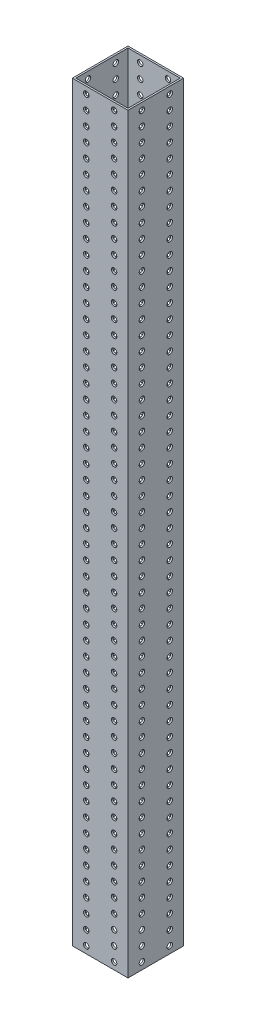
SolidWorks part; units mm, degrees
ref_plane "Front Plane" through (0, 0, 0) normal (0, 0, 1) x (1, 0, 0)
ref_plane "Top Plane" through (0, 0, 0) normal (0, 1, 0) x (1, 0, 0)
ref_plane "Right Plane" through (0, 0, 0) normal (1, 0, 0) x (0, 0, -1)
sketch "Sketch1" plane through (0, 0, 0) normal (0, 1, 0) x (1, 0, 0)
  line L1 (-25.4, 25.4) -> (25.4, 25.4)
  line L2 (-25.4, 25.4) -> (-25.4, -25.4)
  line L3 (-25.4, -25.4) -> (25.4, -25.4)
  line L4 (25.4, 25.4) -> (25.4, -25.4)
  line L5 (-25.4, 25.4) -> (25.4, -25.4) construction
  line L6 (-25.4, -25.4) -> (25.4, 25.4) construction
  line L7 (23.8125, 23.8125) -> (-23.8125, 23.8125)
  line L8 (23.8125, 23.8125) -> (23.8125, -23.8125)
  line L9 (23.8125, -23.8125) -> (-23.8125, -23.8125)
  line L10 (-23.8125, 23.8125) -> (-23.8125, -23.8125)
  line L11 (23.8125, 23.8125) -> (-23.8125, -23.8125) construction
  line L12 (23.8125, -23.8125) -> (-23.8125, 23.8125) construction
  point P0 (0, 0)
  point P6 (0, 0)
  dimension "D1" = 50.8
  dimension "D2" = 50.8
  dimension "D3" = 1.5875
  dimension "D4" = 1.5875
extrude "Boss-Extrude1" add sketch "Sketch1" along normal blind 685.8
sketch "Sketch2" plane through (0, 0, 25.4) normal (0, 0, 1) x (1, 0, 0)
  line L0 (0, 685.8) -> (0, 0) construction
  line L1 (-25.4, 685.8) -> (25.4, 685.8) construction
  line L2 (-25.4, 685.8) -> (-25.4, 0) construction
  circle A0 centre (-12.7, 679.45) radius 2.4892
  circle A1 centre (-12.7, 666.75) radius 2.4892
  circle A2 centre (-12.7, 654.05) radius 2.4892
  circle A3 centre (-12.7, 641.35) radius 2.4892
  circle A4 centre (-12.7, 628.65) radius 2.4892
  circle A5 centre (-12.7, 615.95) radius 2.4892
  circle A6 centre (-12.7, 603.25) radius 2.4892
  circle A7 centre (-12.7, 590.55) radius 2.4892
  circle A8 centre (-12.7, 577.85) radius 2.4892
  circle A9 centre (-12.7, 565.15) radius 2.4892
  circle A10 centre (-12.7, 552.45) radius 2.4892
  circle A11 centre (-12.7, 539.75) radius 2.4892
  circle A12 centre (-12.7, 527.05) radius 2.4892
  circle A13 centre (-12.7, 514.35) radius 2.4892
  circle A14 centre (-12.7, 501.65) radius 2.4892
  circle A15 centre (-12.7, 488.95) radius 2.4892
  circle A16 centre (-12.7, 476.25) radius 2.4892
  circle A17 centre (-12.7, 463.55) radius 2.4892
  circle A18 centre (-12.7, 450.85) radius 2.4892
  circle A19 centre (-12.7, 438.15) radius 2.4892
  circle A20 centre (-12.7, 425.45) radius 2.4892
  circle A21 centre (-12.7, 412.75) radius 2.4892
  circle A22 centre (-12.7, 400.05) radius 2.4892
  circle A23 centre (-12.7, 387.35) radius 2.4892
  circle A24 centre (-12.7, 374.65) radius 2.4892
  circle A25 centre (-12.7, 361.95) radius 2.4892
  circle A26 centre (-12.7, 349.25) radius 2.4892
  circle A27 centre (-12.7, 336.55) radius 2.4892
  circle A28 centre (-12.7, 323.85) radius 2.4892
  circle A29 centre (-12.7, 311.15) radius 2.4892
  circle A30 centre (-12.7, 298.45) radius 2.4892
  circle A31 centre (-12.7, 285.75) radius 2.4892
  circle A32 centre (-12.7, 273.05) radius 2.4892
  circle A33 centre (-12.7, 260.35) radius 2.4892
  circle A34 centre (-12.7, 247.65) radius 2.4892
  circle A35 centre (-12.7, 234.95) radius 2.4892
  circle A36 centre (-12.7, 222.25) radius 2.4892
  circle A37 centre (-12.7, 209.55) radius 2.4892
  circle A38 centre (-12.7, 196.85) radius 2.4892
  circle A39 centre (-12.7, 184.15) radius 2.4892
  circle A40 centre (-12.7, 171.45) radius 2.4892
  circle A41 centre (-12.7, 158.75) radius 2.4892
  circle A42 centre (-12.7, 146.05) radius 2.4892
  circle A43 centre (-12.7, 133.35) radius 2.4892
  circle A44 centre (-12.7, 120.65) radius 2.4892
  circle A45 centre (-12.7, 107.95) radius 2.4892
  circle A46 centre (-12.7, 95.25) radius 2.4892
  circle A47 centre (-12.7, 82.55) radius 2.4892
  circle A48 centre (-12.7, 69.85) radius 2.4892
  circle A49 centre (-12.7, 57.15) radius 2.4892
  circle A50 centre (-12.7, 44.45) radius 2.4892
  circle A51 centre (-12.7, 31.75) radius 2.4892
  circle A52 centre (-12.7, 19.05) radius 2.4892
  circle A53 centre (-12.7, 6.35) radius 2.4892
  circle A54 centre (12.7, 6.35) radius 2.4892
  circle A55 centre (12.7, 19.05) radius 2.4892
  circle A56 centre (12.7, 31.75) radius 2.4892
  circle A57 centre (12.7, 44.45) radius 2.4892
  circle A58 centre (12.7, 57.15) radius 2.4892
  circle A59 centre (12.7, 69.85) radius 2.4892
  circle A60 centre (12.7, 82.55) radius 2.4892
  circle A61 centre (12.7, 95.25) radius 2.4892
  circle A62 centre (12.7, 107.95) radius 2.4892
  circle A63 centre (12.7, 120.65) radius 2.4892
  circle A64 centre (12.7, 133.35) radius 2.4892
  circle A65 centre (12.7, 146.05) radius 2.4892
  circle A66 centre (12.7, 158.75) radius 2.4892
  circle A67 centre (12.7, 171.45) radius 2.4892
  circle A68 centre (12.7, 184.15) radius 2.4892
  circle A69 centre (12.7, 196.85) radius 2.4892
  circle A70 centre (12.7, 209.55) radius 2.4892
  circle A71 centre (12.7, 222.25) radius 2.4892
  circle A72 centre (12.7, 234.95) radius 2.4892
  circle A73 centre (12.7, 247.65) radius 2.4892
  circle A74 centre (12.7, 260.35) radius 2.4892
  circle A75 centre (12.7, 273.05) radius 2.4892
  circle A76 centre (12.7, 285.75) radius 2.4892
  circle A77 centre (12.7, 298.45) radius 2.4892
  circle A78 centre (12.7, 311.15) radius 2.4892
  circle A79 centre (12.7, 323.85) radius 2.4892
  circle A80 centre (12.7, 336.55) radius 2.4892
  circle A81 centre (12.7, 374.65) radius 2.4892
  circle A82 centre (12.7, 361.95) radius 2.4892
  circle A83 centre (12.7, 349.25) radius 2.4892
  circle A84 centre (12.7, 387.35) radius 2.4892
  circle A85 centre (12.7, 400.05) radius 2.4892
  circle A86 centre (12.7, 412.75) radius 2.4892
  circle A87 centre (12.7, 425.45) radius 2.4892
  circle A88 centre (12.7, 438.15) radius 2.4892
  circle A89 centre (12.7, 450.85) radius 2.4892
  circle A90 centre (12.7, 463.55) radius 2.4892
  circle A91 centre (12.7, 476.25) radius 2.4892
  circle A92 centre (12.7, 488.95) radius 2.4892
  circle A93 centre (12.7, 501.65) radius 2.4892
  circle A94 centre (12.7, 514.35) radius 2.4892
  circle A95 centre (12.7, 527.05) radius 2.4892
  circle A96 centre (12.7, 539.75) radius 2.4892
  circle A97 centre (12.7, 552.45) radius 2.4892
  circle A98 centre (12.7, 565.15) radius 2.4892
  circle A99 centre (12.7, 577.85) radius 2.4892
  circle A100 centre (12.7, 590.55) radius 2.4892
  circle A101 centre (12.7, 603.25) radius 2.4892
  circle A102 centre (12.7, 615.95) radius 2.4892
  circle A103 centre (12.7, 628.65) radius 2.4892
  circle A104 centre (12.7, 641.35) radius 2.4892
  circle A105 centre (12.7, 654.05) radius 2.4892
  circle A106 centre (12.7, 666.75) radius 2.4892
  circle A107 centre (12.7, 679.45) radius 2.4892
  dimension "D1" = 4.9784
  dimension "D2" = 6.35
  dimension "D3" = 12.7
  dimension "D5" = 12.7
  dimension "D4" = 54
extrude "Cut-Extrude1" cut sketch "Sketch2" against normal through all
sketch "Sketch4" plane through (25.4, 0, 0) normal (1, 0, 0) x (0, 0, -1)
  line L0 (0, 685.8) -> (0, 0) construction
  line L1 (-25.4, 685.8) -> (25.4, 685.8) construction
  line L2 (-25.4, 685.8) -> (-25.4, 0) construction
  circle A0 centre (-12.7, 679.45) radius 2.4892
  circle A1 centre (-12.7, 666.75) radius 2.4892
  circle A2 centre (-12.7, 654.05) radius 2.4892
  circle A3 centre (-12.7, 641.35) radius 2.4892
  circle A4 centre (-12.7, 628.65) radius 2.4892
  circle A5 centre (-12.7, 615.95) radius 2.4892
  circle A6 centre (-12.7, 603.25) radius 2.4892
  circle A7 centre (-12.7, 590.55) radius 2.4892
  circle A8 centre (-12.7, 577.85) radius 2.4892
  circle A9 centre (-12.7, 565.15) radius 2.4892
  circle A10 centre (-12.7, 552.45) radius 2.4892
  circle A11 centre (-12.7, 539.75) radius 2.4892
  circle A12 centre (-12.7, 527.05) radius 2.4892
  circle A13 centre (-12.7, 514.35) radius 2.4892
  circle A14 centre (-12.7, 501.65) radius 2.4892
  circle A15 centre (-12.7, 488.95) radius 2.4892
  circle A16 centre (-12.7, 476.25) radius 2.4892
  circle A17 centre (-12.7, 463.55) radius 2.4892
  circle A18 centre (-12.7, 450.85) radius 2.4892
  circle A19 centre (-12.7, 438.15) radius 2.4892
  circle A20 centre (-12.7, 425.45) radius 2.4892
  circle A21 centre (-12.7, 412.75) radius 2.4892
  circle A22 centre (-12.7, 400.05) radius 2.4892
  circle A23 centre (-12.7, 387.35) radius 2.4892
  circle A24 centre (-12.7, 374.65) radius 2.4892
  circle A25 centre (-12.7, 361.95) radius 2.4892
  circle A26 centre (-12.7, 349.25) radius 2.4892
  circle A27 centre (-12.7, 336.55) radius 2.4892
  circle A28 centre (-12.7, 323.85) radius 2.4892
  circle A29 centre (-12.7, 311.15) radius 2.4892
  circle A30 centre (-12.7, 298.45) radius 2.4892
  circle A31 centre (-12.7, 285.75) radius 2.4892
  circle A32 centre (-12.7, 273.05) radius 2.4892
  circle A33 centre (-12.7, 260.35) radius 2.4892
  circle A34 centre (-12.7, 247.65) radius 2.4892
  circle A35 centre (-12.7, 234.95) radius 2.4892
  circle A36 centre (-12.7, 222.25) radius 2.4892
  circle A37 centre (-12.7, 209.55) radius 2.4892
  circle A38 centre (-12.7, 196.85) radius 2.4892
  circle A39 centre (-12.7, 184.15) radius 2.4892
  circle A40 centre (-12.7, 171.45) radius 2.4892
  circle A41 centre (-12.7, 158.75) radius 2.4892
  circle A42 centre (-12.7, 146.05) radius 2.4892
  circle A43 centre (-12.7, 133.35) radius 2.4892
  circle A44 centre (-12.7, 120.65) radius 2.4892
  circle A45 centre (-12.7, 107.95) radius 2.4892
  circle A46 centre (-12.7, 95.25) radius 2.4892
  circle A47 centre (-12.7, 82.55) radius 2.4892
  circle A48 centre (-12.7, 69.85) radius 2.4892
  circle A49 centre (-12.7, 57.15) radius 2.4892
  circle A50 centre (-12.7, 44.45) radius 2.4892
  circle A51 centre (-12.7, 31.75) radius 2.4892
  circle A52 centre (-12.7, 19.05) radius 2.4892
  circle A53 centre (-12.7, 6.35) radius 2.4892
  circle A54 centre (12.7, 273.05) radius 2.4892
  circle A55 centre (12.7, 285.75) radius 2.4892
  circle A56 centre (12.7, 298.45) radius 2.4892
  circle A57 centre (12.7, 311.15) radius 2.4892
  circle A58 centre (12.7, 323.85) radius 2.4892
  circle A59 centre (12.7, 336.55) radius 2.4892
  circle A60 centre (12.7, 349.25) radius 2.4892
  circle A61 centre (12.7, 361.95) radius 2.4892
  circle A62 centre (12.7, 374.65) radius 2.4892
  circle A63 centre (12.7, 387.35) radius 2.4892
  circle A64 centre (12.7, 400.05) radius 2.4892
  circle A65 centre (12.7, 412.75) radius 2.4892
  circle A66 centre (12.7, 425.45) radius 2.4892
  circle A67 centre (12.7, 438.15) radius 2.4892
  circle A68 centre (12.7, 450.85) radius 2.4892
  circle A69 centre (12.7, 463.55) radius 2.4892
  circle A70 centre (12.7, 476.25) radius 2.4892
  circle A71 centre (12.7, 488.95) radius 2.4892
  circle A72 centre (12.7, 501.65) radius 2.4892
  circle A73 centre (12.7, 514.35) radius 2.4892
  circle A74 centre (12.7, 527.05) radius 2.4892
  circle A75 centre (12.7, 539.75) radius 2.4892
  circle A76 centre (12.7, 552.45) radius 2.4892
  circle A77 centre (12.7, 565.15) radius 2.4892
  circle A78 centre (12.7, 577.85) radius 2.4892
  circle A79 centre (12.7, 590.55) radius 2.4892
  circle A80 centre (12.7, 603.25) radius 2.4892
  circle A81 centre (12.7, 615.95) radius 2.4892
  circle A82 centre (12.7, 628.65) radius 2.4892
  circle A83 centre (12.7, 641.35) radius 2.4892
  circle A84 centre (12.7, 654.05) radius 2.4892
  circle A85 centre (12.7, 666.75) radius 2.4892
  circle A86 centre (12.7, 19.05) radius 2.4892
  circle A87 centre (12.7, 31.75) radius 2.4892
  circle A88 centre (12.7, 44.45) radius 2.4892
  circle A89 centre (12.7, 57.15) radius 2.4892
  circle A90 centre (12.7, 69.85) radius 2.4892
  circle A91 centre (12.7, 82.55) radius 2.4892
  circle A92 centre (12.7, 95.25) radius 2.4892
  circle A93 centre (12.7, 107.95) radius 2.4892
  circle A94 centre (12.7, 120.65) radius 2.4892
  circle A95 centre (12.7, 133.35) radius 2.4892
  circle A96 centre (12.7, 146.05) radius 2.4892
  circle A97 centre (12.7, 158.75) radius 2.4892
  circle A98 centre (12.7, 171.45) radius 2.4892
  circle A99 centre (12.7, 184.15) radius 2.4892
  circle A100 centre (12.7, 196.85) radius 2.4892
  circle A101 centre (12.7, 209.55) radius 2.4892
  circle A102 centre (12.7, 222.25) radius 2.4892
  circle A103 centre (12.7, 234.95) radius 2.4892
  circle A104 centre (12.7, 247.65) radius 2.4892
  circle A105 centre (12.7, 260.35) radius 2.4892
  circle A106 centre (12.7, 6.35) radius 2.4892
  circle A107 centre (12.7, 679.45) radius 2.4892
  dimension "D1" = 4.9784
  dimension "D2" = 12.7
  dimension "D3" = 6.35
  dimension "D5" = 12.7
  dimension "D4" = 54
extrude "Cut-Extrude2" cut sketch "Sketch4" against normal through all
sketch "Sketch5" plane through (25.4, 0, 0) normal (1, 0, 0) x (0, 0, -1)
  line L0 (25.4, 685.8) -> (25.4, 0) construction
  line L1 (-25.4, 685.8) -> (25.4, 685.8)
  line L2 (-25.4, 685.8) -> (-25.4, 114.3)
  line L3 (-25.4, 114.3) -> (25.4, 114.3)
  line L4 (25.4, 685.8) -> (25.4, 114.3)
  dimension "D1" = 571.5
